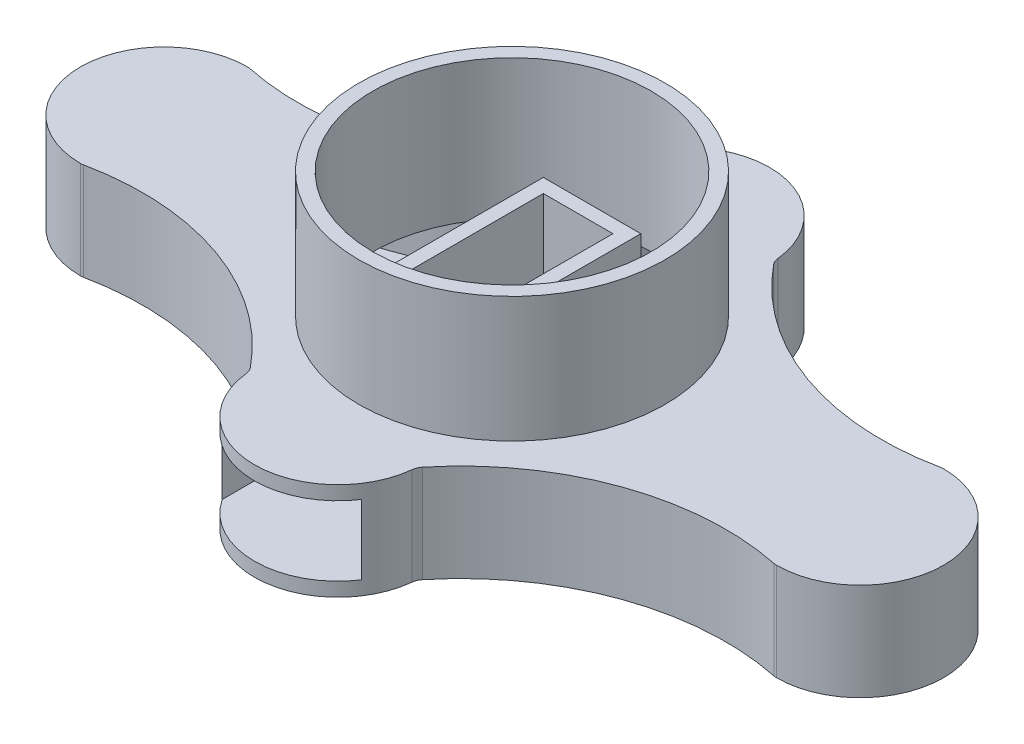
SolidWorks part; units mm, degrees
ref_plane "Front Plane" through (0, 0, 0) normal (0, 0, 1) x (1, 0, 0)
ref_plane "Top Plane" through (0, 0, 0) normal (0, 1, 0) x (1, 0, 0)
ref_plane "Right Plane" through (0, 0, 0) normal (1, 0, 0) x (0, 0, -1)
sketch "Sketch9" plane through (0, 0, 0) normal (0, 1, 0) x (1, 0, 0)
  line L0 (0, 31.75) -> (0, -31.75) construction
  line L1 (63.5, 0) -> (-63.5, 0) construction
  arc A0 (-63.5, 12.7) -> (-63.5, -12.7) centre (-63.5, 0) ccw
  arc A1 (12.7, 31.75) -> (-12.7, 31.75) centre (0, 31.75) ccw
  arc A2 (63.5, -12.7) -> (63.5, 12.7) centre (63.5, 0) ccw
  arc A3 (-12.7, -31.75) -> (12.7, -31.75) centre (0, -31.75) ccw
  arc A4 (-12.7, 31.75) -> (-63.5, 12.7) centre (-53.181, 62.4409) cw
  arc A5 (-63.5, -12.7) -> (-12.7, -31.75) centre (-53.181, -62.4409) cw
  arc A6 (12.7, -31.75) -> (63.5, -12.7) centre (53.181, -62.4409) cw
  arc A7 (63.5, 12.7) -> (12.7, 31.75) centre (53.181, 62.4409) cw
  point P1 (0, 0)
  point P6 (0, 0)
  point P7 (0, 0)
  point P21 (0, 0)
  point P22 (0, 0)
  point P23 (-55.9881, -25.4)
  point P25 (-63.5, -12.7)
  dimension "D1" = 12.7
  dimension "D4" = 50.8
  dimension "D2" = 127
  dimension "D3" = 63.5
extrude "Boss-Extrude6" add sketch "Sketch9" along normal blind 12.7 contours A2 A7 A1 A4 A0 A5 A3 A6 region at (0, 0, 0)
sketch "Sketch10" plane through (0, 12.7, 0) normal (0, 1, 0) x (1, 0, 0)
  circle A0 centre (0, 0) radius 25.4
  dimension "D1" = 50.8
extrude "Boss-Extrude7" add sketch "Sketch10" along normal blind 25.4
shell "Shell14" thickness 2.54 removed face at (0, 38.1, 25.4) outward yes
fillet "Fillet1" radius 2.54 8 edges at (-15.2134, 6.35, 32.6501) (-63.2242, 6.35, 15.2375) (-15.2134, 6.35, -32.6501) (-63.2242, 6.35, -15.2375) (15.2134, 6.35, -32.6501) (63.2242, 6.35, -15.2375) (15.2134, 6.35, 32.6501) (63.2242, 6.35, 15.2375)
sketch "Sketch11" plane through (0, 0, 0) normal (0, 1, 0) x (1, 0, 0)
  line L0 (8.89, 14.605) -> (8.89, -14.605)
  line L1 (-6.35, 12.065) -> (6.35, 12.065)
  line L2 (-6.35, 12.065) -> (-6.35, -12.065)
  line L3 (-6.35, -12.065) -> (6.35, -12.065)
  line L4 (6.35, 12.065) -> (6.35, -12.065)
  line L5 (-6.35, 12.065) -> (6.35, -12.065) construction
  line L6 (-6.35, -12.065) -> (6.35, 12.065) construction
  line L7 (-8.89, -14.605) -> (8.89, -14.605)
  line L8 (-8.89, 14.605) -> (-8.89, -14.605)
  line L9 (-8.89, 14.605) -> (8.89, 14.605)
  point P0 (0, 0)
  dimension "D1" = 12.7
  dimension "D2" = 24.13
  dimension "D3" = 2.54
extrude "Boss-Extrude8" add sketch "Sketch11" along normal blind 25.4
sketch "Sketch12" plane through (0, 25.4, 0) normal (0, 1, 0) x (1, 0, 0)
  line L0 (-6.35, -12.065) -> (6.35, -12.065) construction
  line L1 (6.35, -12.065) -> (-6.35, -12.065)
  line L2 (6.35, -12.065) -> (6.35, -14.605)
  line L3 (6.35, -14.605) -> (-6.35, -14.605)
  line L4 (-6.35, -12.065) -> (-6.35, -14.605)
  line L5 (-8.89, -14.605) -> (8.89, -14.605) construction
extrude "Cut-Extrude6" cut sketch "Sketch12" against normal up to surface (25.4 mm away) up to face at (0, 0, 0)
sketch "Sketch15" plane through (0, 0, 14.605) normal (0, 0, 1) x (1, 0, 0)
  line L0 (-12.7, 6.35) -> (-15.1545, 6.35) construction
  line L1 (-12.7, 12.7) -> (12.7, 12.7)
  line L2 (-12.7, 12.7) -> (-12.7, 0)
  line L3 (-12.7, 0) -> (12.7, 0)
  line L4 (12.7, 12.7) -> (12.7, 0)
  line L5 (-12.7, 12.7) -> (12.7, 0) construction
  line L6 (-12.7, 0) -> (12.7, 12.7) construction
  line L8 (12.7, 6.35) -> (15.1545, 6.35) construction
  line L9 (15.1545, -2.54) -> (15.1545, 15.24) construction
  line L10 (-15.1545, 15.24) -> (-15.1545, -2.54) construction
  point P0 (0, 6.35)
  dimension "D1" = 25.4
  dimension "D2" = 12.7
extrude "Cut-Extrude7" cut sketch "Sketch15" along normal up to surface (25.5692 mm away) up to face at (0, 6.35, 40.1761)
